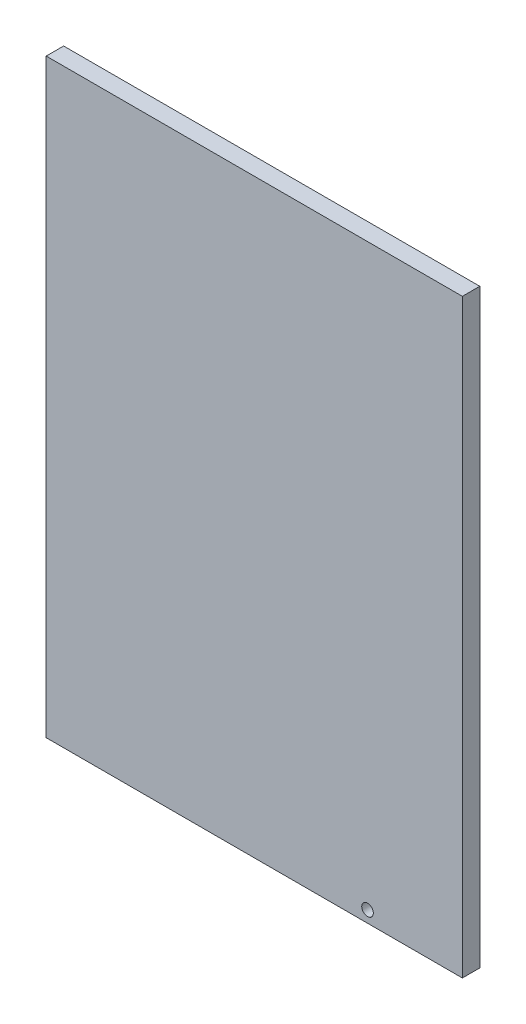
SolidWorks part; units mm, degrees
ref_plane "Front Plane" through (0, 0, 0) normal (0, 0, 1) x (1, 0, 0)
ref_plane "Top Plane" through (0, 0, 0) normal (0, 1, 0) x (1, 0, 0)
ref_plane "Right Plane" through (0, 0, 0) normal (1, 0, 0) x (0, 0, -1)
sketch "Sketch1" plane through (0, 0, 0) normal (0, 0, 1) x (1, 0, 0)
  line L1 (-107.5, -152.5) -> (107.5, -152.5)
  line L2 (-107.5, -152.5) -> (-107.5, 152.5)
  line L3 (-107.5, 152.5) -> (107.5, 152.5)
  line L4 (107.5, -152.5) -> (107.5, 152.5)
  line L5 (-107.5, -152.5) -> (107.5, 152.5) construction
  line L6 (-107.5, 152.5) -> (107.5, -152.5) construction
  point P0 (0, 0)
  dimension "D1" = 215
  dimension "D2" = 305
extrude "Boss-Extrude1" add sketch "Sketch1" along normal blind 9
sketch "Sketch2" plane through (0, 0, 9) normal (0, 0, 1) x (1, 0, 0)
  line L0 (107.5, -152.5) -> (107.5, 152.5) construction
  line L1 (-107.5, -152.5) -> (107.5, -152.5) construction
  circle A0 centre (58.5, -146.5) radius 3
  dimension "D1" = 6
  dimension "D2" = 49
  dimension "D3" = 6
extrude "Cut-Extrude1" cut sketch "Sketch2" against normal through all
equation "\"PCLength\"= 320mm'Length across I/O from PS to GPU"
equation "\"PCWidth\"= 242mm'Distance of longest part parallel to GPU(ussually GPU)"
equation "\"PCHeight\"= 172mm'Tallest point with mobo laying flat"
equation "\"WallThickness\"= 9mm'Thickness of each outer tank wall"
equation "\"ThermoBarrierThickness\"= 3mm'Thickness of barrier between hot side and cold side"
equation "\"HotSideGap\"= 40mm'Space in the hot side for a pump"
equation "\"PCClearance\"= 30mm'Clearance from top of tank to top of PC"
equation "\"RadiatorHeight\"= 275mm'Final Height from ground of radiators"
equation "\"D1@Sketch1\"=\"PCHeight\" + \"ThermoBarrierThickness\" + \"HotSideGap\""
equation "\"D2@Sketch1\"=\"RadiatorHeight\" + \"PCClearance\""
equation "\"D1@Boss-Extrude1\"=\"WallThickness\""
equation "\"D2@Sketch2\"=\"HotSideGap\" + \"ThermoBarrierThickness\" + 6"
